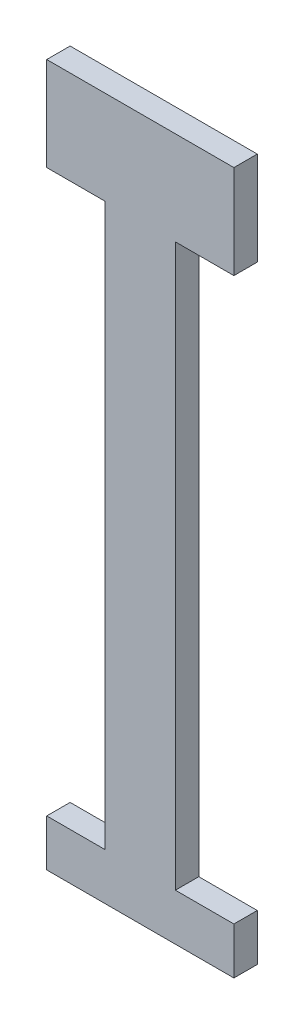
SolidWorks part; units mm, degrees
ref_plane "Front Plane" through (0, 0, 0) normal (0, 0, 1) x (1, 0, 0)
ref_plane "Top Plane" through (0, 0, 0) normal (0, 1, 0) x (1, 0, 0)
ref_plane "Right Plane" through (0, 0, 0) normal (1, 0, 0) x (0, 0, -1)
sketch "Sketch1" plane through (0, 0, 0) normal (0, 0, 1) x (1, 0, 0)
  line L0 (4.7625, 50.8) -> (4.7625, 0) construction
  line L1 (-7.9375, 0) -> (0, 0)
  line L2 (0, 0) -> (0, 76.2)
  line L3 (-7.9375, 76.2) -> (0, 76.2)
  line L4 (9.525, 0) -> (9.525, 76.2)
  line L5 (-7.9375, -6.35) -> (17.4625, -6.35)
  line L6 (-7.9375, 88.9) -> (-7.9375, 76.2)
  line L7 (17.4625, 88.9) -> (17.4625, 76.2)
  line L8 (0, -6.35) -> (9.525, -6.35) construction
  line L9 (-7.9375, 50.8) -> (-7.9375, 0) construction
  line L10 (17.4625, 50.8) -> (17.4625, 0) construction
  line L11 (0, 0) -> (9.525, 0) construction
  line L12 (9.525, 0) -> (17.4625, 0)
  line L13 (-7.9375, 88.9) -> (17.4625, 88.9)
  line L14 (0, 88.9) -> (9.525, 88.9) construction
  line L15 (0, 76.2) -> (9.525, 76.2) construction
  line L16 (9.525, 76.2) -> (17.4625, 76.2)
  line L17 (17.4625, 0) -> (17.4625, -6.35)
  line L18 (-7.9375, 0) -> (-7.9375, -6.35)
  dimension "D1" = 9.525
  dimension "D2" = 76.2
  dimension "D3" = 6.35
  dimension "D4" = 12.7
  dimension "D5" = 12.7
  dimension "D6" = 12.7
extrude "Extrude1" add sketch "Sketch1" along normal blind 3.175
